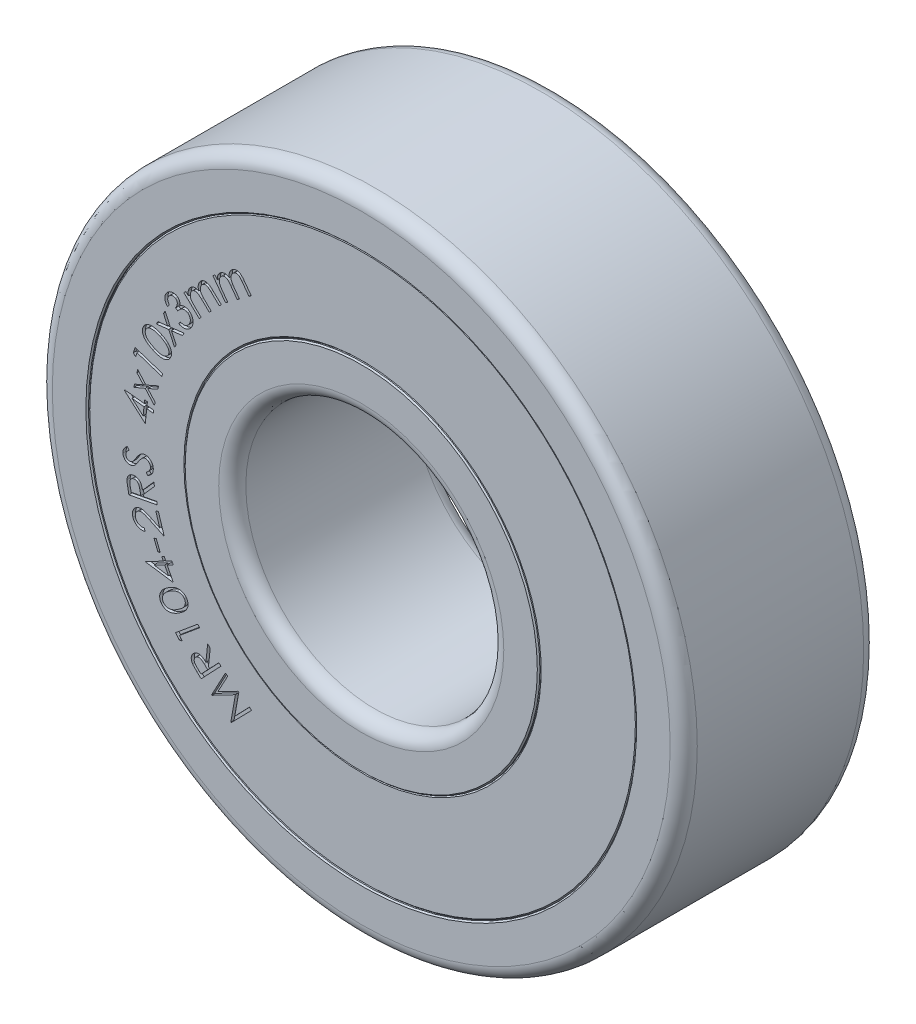
SolidWorks part; units mm, degrees
material "AISI 316 Annealed Stainless Steel Bar (SS)"
ref_plane "Front" through (0, 0, 0) normal (0, 0, 1) x (1, 0, 0)
ref_plane "Top" through (0, 0, 0) normal (0, 1, 0) x (1, 0, 0)
ref_plane "Right" through (0, 0, 0) normal (1, 0, 0) x (0, 0, -1)
sketch "LAYOUT R" plane through (0, 0, 0) normal (1, 0, 0) x (0, 0, -1)
  line L0 (-1.5, 2) -> (1.5, 2)
  line L1 (1.5, -5) -> (-1.5, -5) construction
  line L2 (1.5, -5) -> (1.5, 5) construction
  line L3 (1.5, 5) -> (-1.5, 5)
  line L4 (-1.5, -5) -> (-1.5, 5) construction
  line L5 (1.5, -5) -> (-1.5, 5) construction
  line L6 (1.5, 5) -> (-1.5, -5) construction
  line L7 (-1.5, 2.75) -> (1.5, 2.75)
  line L8 (-1.5, 4.25) -> (1.5, 4.25)
  line L11 (-17.5, 0) -> (17.5, 0) construction
  line L12 (-1.5, 5) -> (-1.5, 4.25)
  line L13 (1.5, 5) -> (1.5, 4.25)
  line L14 (-1.5, 4.25) -> (-1.5, 2.75)
  line L15 (1.5, 4.25) -> (1.5, 2.75)
  line L16 (-1.5, 2.75) -> (-1.5, 2)
  line L17 (1.5, 2.75) -> (1.5, 2)
  line L18 (-1.48, 4.25) -> (-1.48, 2.75)
  line L19 (1.48, 4.25) -> (1.48, 2.75)
  point P0 (0, 0)
  point P15 (0, 0)
  dimension "D1" = 3
  dimension "D2" = 10
  dimension "D3" = 2
  dimension "D6" = 0.02
  dimension "D7" = 0.02
  dimension "D4" = 2.75
  dimension "D5" = 4.25
sketch "Sketch R, INNER BODY" plane through (0, 0, 0) normal (1, 0, 0) x (0, 0, -1)
  line L0 (-1.5, 2) -> (1.5, 2) construction
  line L2 (-1.5, 2.75) -> (1.5, 2.75) construction
  line L4 (-1.5, 2) -> (1.5, 2)
  line L6 (-1.5, 2.75) -> (1.5, 2.75)
  line L8 (1.5, 2.75) -> (1.5, 2) construction
  line L9 (-1.5, 2.75) -> (-1.5, 2) construction
  line L10 (1.5, 2.75) -> (1.5, 2)
  line L11 (-1.5, 2.75) -> (-1.5, 2)
  line L12 (-17.5, 0) -> (17.5, 0) construction
  line L13 (-17.5, 0) -> (17.5, 0) construction
sketch "Sketch R, OUTER BODY" plane through (0, 0, 0) normal (1, 0, 0) x (0, 0, -1)
  line L2 (-1.5, 4.25) -> (1.5, 4.25) construction
  line L3 (1.5, 5) -> (-1.5, 5) construction
  line L6 (-1.5, 4.25) -> (1.5, 4.25)
  line L7 (1.5, 5) -> (-1.5, 5)
  line L8 (-17.5, 0) -> (17.5, 0) construction
  line L9 (-17.5, 0) -> (17.5, 0) construction
  line L10 (1.5, 5) -> (1.5, 4.25) construction
  line L11 (-1.5, 5) -> (-1.5, 4.25) construction
  line L12 (1.5, 5) -> (1.5, 4.25)
  line L13 (-1.5, 5) -> (-1.5, 4.25)
sketch "Sketch R, SEAL FACES" plane through (0, 0, 0) normal (1, 0, 0) x (0, 0, -1)
  line L0 (-17.5, 0) -> (17.5, 0) construction
  line L1 (-17.5, 0) -> (17.5, 0) construction
  line L3 (-1.5, 2.75) -> (1.5, 2.75) construction
  line L5 (-1.5, 4.25) -> (1.5, 4.25) construction
  line L7 (-1.48, 2.75) -> (1.48, 2.75)
  line L9 (-1.48, 4.25) -> (1.48, 4.25)
  line L10 (1.48, 4.25) -> (1.48, 2.75) construction
  line L11 (-1.48, 4.25) -> (-1.48, 2.75) construction
  line L12 (1.48, 4.25) -> (1.48, 2.75)
  line L13 (-1.48, 4.25) -> (-1.48, 2.75)
revolve "Revolve INNER BODY" add sketch "Sketch R, INNER BODY" angle 360 about L13
fillet "Fillet INNER BODY" radius 0.21 2 edges at (2, 0, 1.5) (2, 0, -1.5)
chamfer "Chamfer INNER BODY" distance 0.02 angle 45 2 edges at (2.75, 0, -1.5) (2.75, 0, 1.5)
revolve "Revolve OUTER BODY" add sketch "Sketch R, OUTER BODY" angle 360 about L9
fillet "Fillet OUTER BODY" radius 0.21 2 edges at (5, 0, -1.5) (5, 0, 1.5)
chamfer "Chamfer OUTER BODY" distance 0.02 angle 45 2 edges at (4.25, 0, 1.5) (4.25, 0, -1.5)
revolve "Revolve SEALS" add sketch "Sketch R, SEAL FACES" angle 360 about L1
chamfer "Chamfer SEALS" distance 0.02 angle 45 4 edges at (2.75, 0, -1.48) (4.25, 0, -1.48) (4.25, 0, 1.48) (2.75, 0, 1.48)
sketch "Sketch TEXT RADIUS 1 — MANUALLY ASSIGN TEXT AND FONT SIZE (FROM EQUATIONS)" plane through (0, 0, 1.48) normal (0, 0, 1) x (1, 0, 0)
  circle A0 centre (0, 0) radius 3.275 construction
  text T0 "MR104-2RS  4x10x3mm" font "Century Gothic" height 0.45
  dimension "D1" = 6.55
extrude "Cut-Extrude SEAL LABEL 1" cut sketch "Sketch TEXT RADIUS 1 — MANUALLY ASSIGN TEXT AND FONT SIZE (FROM EQUATIONS)" against normal blind 0.05
sketch "Sketch TEXT RADIUS 2 — MANUALLY ASSIGN TEXT AND FONT SIZE (FROM EQUATIONS)" plane through (0, 0, -1.48) normal (0, 0, -1) x (-1, 0, 0)
  circle A0 centre (0, 0) radius 3.275 construction
  text T0 "MR104-2RS  4x10x3mm\r\n" font "Century Gothic" height 0.45
  dimension "D1" = 6.55
extrude "Cut-Extrude SEAL LABEL 2" cut sketch "Sketch TEXT RADIUS 2 — MANUALLY ASSIGN TEXT AND FONT SIZE (FROM EQUATIONS)" against normal blind 0.05
equation "\"_i__BORE\"= 4"
equation "\"_i__OUTSIDE_DIAMETER\"= 10"
equation "\"_i__WIDTH\"= 3"
equation "\"_i_optional__TEXT_RADIUS_ADJUSTMENT\"= 0"
equation "\"_output__FONT_SIZE_mm\"= \"BODY_SPAN__SEAL__OF_RADIUS\" * \"param__FONT_SIZE_RATIO\"'MANUALLY ASSIGN TO FONT"
equation "\"BODY__HALF_WIDTH\"= \"_i__WIDTH\" / 2"
equation "\"BODY_SPAN___OF_DIAMETER\"= \"_i__OUTSIDE_DIAMETER\" - \"_i__BORE\""
equation "\"BODY_SPAN___OF_RADIUS\"= \"BODY_SPAN___OF_DIAMETER\" / 2"
equation "\"BODY_SPAN__BORE_AND_OD__OF RADIUS\"= ( \"BODY_SPAN___OF_RADIUS\" - \"BODY_SPAN__SEAL__OF_RADIUS\" ) / 2"
equation "\"BODY_SPAN__SEAL__OF_RADIUS\"= \"BODY_SPAN___OF_RADIUS\" * \"param__SEAL_PANEL_SPAN__RATIO_OF_BODY_RADIAN\""
equation "\"BORE__RADIUS\"= \"_i__BORE\" / 2"
equation "\"CORNER_RADII\"= \"_i__WIDTH\" * \"param__CORNER_RADII__ISO_MAX_RATIO_TO_WIDTH\""
equation "\"param__CORNER_RADII__ISO_MAX_RATIO_TO_WIDTH\"= 0.07'WHERE WIDTH IS LESS THAN DIAMETER"
equation "\"param__FONT_SIZE_RATIO\"= 0.3"
equation "\"param__SEAL_FACE_INSET__RATIO_OF_WIDTH\"= .01"
equation "\"param__SEAL_PANEL_SPAN__RATIO_OF_BODY_RADIAN\"= 0.5"
equation "\"param__SIDE_CHAMFERS__RATIO_TO_OD\"= 1 / 500"
equation "\"RING_INNER__OUTSIDE_RADIUS\"= \"BORE__RADIUS\" + \"BODY_SPAN__BORE_AND_OD__OF RADIUS\""
equation "\"RING_OUTER__OUTSIDE_RADIUS\"= ( \"_i__OUTSIDE_DIAMETER\" / 2 ) - \"BODY_SPAN__BORE_AND_OD__OF RADIUS\""
equation "\"SEAL_FACE_INSET\"= \"_i__WIDTH\" * \"param__SEAL_FACE_INSET__RATIO_OF_WIDTH\""
equation "\"SIDE_FACE_AND_SEAL_CHAMFERS\"= \"_i__OUTSIDE_DIAMETER\" * \"param__SIDE_CHAMFERS__RATIO_TO_OD\""
equation "\"TEXT_RADIUS\"= \"_i__BORE\" + ( \"BODY_SPAN___OF_DIAMETER\" / 2 ) - \"_output__FONT_SIZE_mm\" + \"_i_optional__TEXT_RADIUS_ADJUSTMENT\""
equation "\"D1@Chamfer INNER BODY\"=\"SIDE_FACE_AND_SEAL_CHAMFERS\""
equation "\"D1@Chamfer OUTER BODY\"=\"SIDE_FACE_AND_SEAL_CHAMFERS\""
equation "\"D1@Chamfer SEALS\"=\"SIDE_FACE_AND_SEAL_CHAMFERS\""
equation "\"D1@Fillet INNER BODY\"=\"CORNER_RADII\""
equation "\"D1@Fillet OUTER BODY\"=\"CORNER_RADII\""
equation "\"D1@LAYOUT R\"=\"_i__WIDTH\""
equation "\"D1@Sketch TEXT RADIUS 1 — MANUALLY ASSIGN TEXT AND FONT SIZE (FROM EQUATIONS)\" = \"TEXT_RADIUS\""
equation "\"D1@Sketch TEXT RADIUS 2 — MANUALLY ASSIGN TEXT AND FONT SIZE (FROM EQUATIONS)\" = \"TEXT_RADIUS\""
equation "\"D2@LAYOUT R\"=\"_i__OUTSIDE_DIAMETER\""
equation "\"D3@LAYOUT R\"=\"BORE__RADIUS\""
equation "\"D4@LAYOUT R\"=\"RING_INNER__OUTSIDE_RADIUS\""
equation "\"D5@LAYOUT R\"=\"RING_OUTER__OUTSIDE_RADIUS\""
